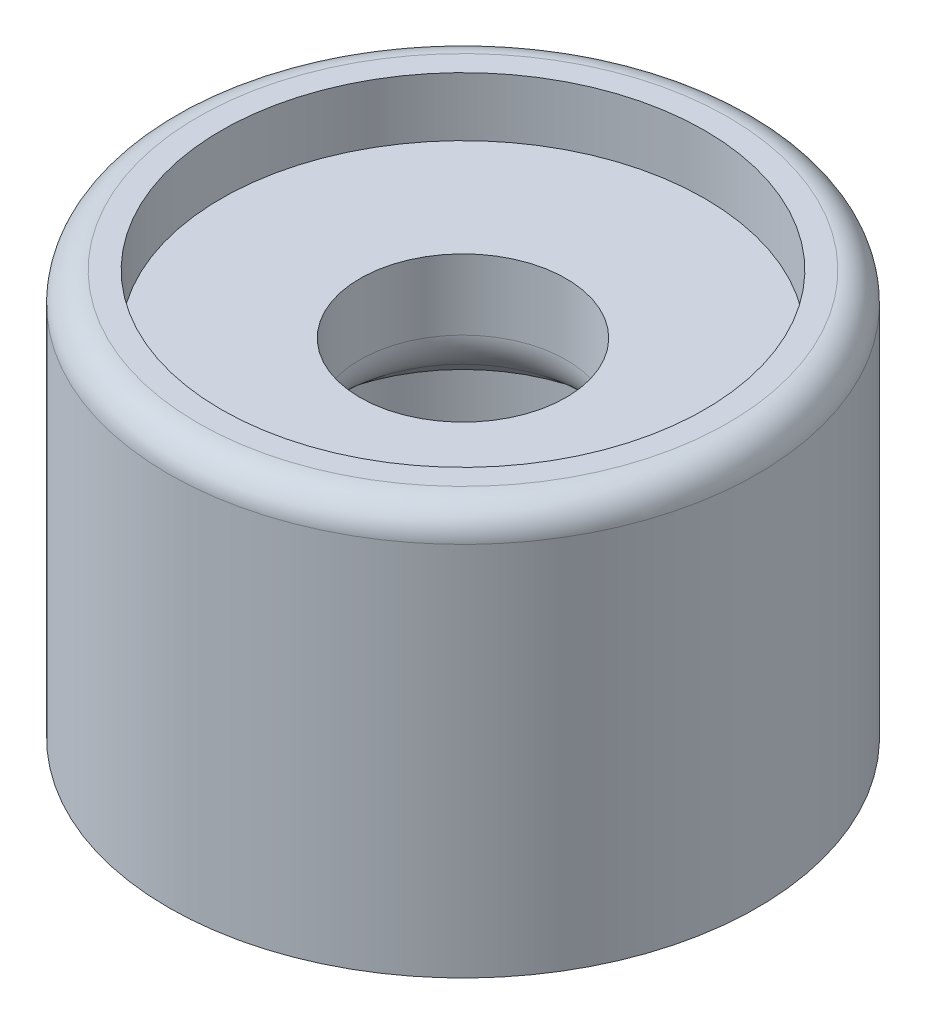
SolidWorks part; units mm, degrees
material "6061-T6 (SS)"
ref_plane "Alzado" through (0, 0, 0) normal (0, 0, 1) x (1, 0, 0)
ref_plane "Planta" through (0, 0, 0) normal (0, 1, 0) x (1, 0, 0)
ref_plane "Vista lateral" through (0, 0, 0) normal (1, 0, 0) x (0, 0, -1)
sketch "Croquis1" plane through (0, 0, 0) normal (0, 1, 0) x (1, 0, 0)
  circle A0 centre (0, 0) radius 3.175
  circle A1 centre (0, 0) radius 6
  dimension "D1" = 12
  dimension "D2" = 6.35
extrude "Saliente-Extruir1" add sketch "Croquis1" along normal blind 4.25
sketch "Croquis2" plane through (0, 0, 0) normal (0, 0, 1) x (1, 0, 0)
  line L0 (-6, 4.25) -> (-6, 5.25)
  line L1 (-6, 5.25) -> (-2.1, 5.25)
  line L2 (-2.1, 5.25) -> (-2.1, 5.15)
  line L3 (-2.1, 5.15) -> (-3.175, 4.25)
  line L4 (6, 4.25) -> (-6, 4.25) construction
  line L5 (0, 0) -> (0, 6.8987) construction
  line L6 (-6, 4.25) -> (-3.175, 4.25)
  dimension "D1" = 4.2
  dimension "D2" = 0.1
  dimension "D3" = 3.9
  dimension "D4" = 1
revolve "Revolución1" add sketch "Croquis2" angle 360 about L5
sketch "Croquis3" plane through (0, 5.25, 0) normal (0, 1, 0) x (1, 0, 0)
  circle A0 centre (0, 0) radius 2.1
  circle A1 centre (0, 0) radius 6
  circle A2 centre (0, 0) radius 6 construction
  circle A3 centre (0, 0) radius 2.1 construction
extrude "Saliente-Extruir2" add sketch "Croquis3" along normal blind 3
fillet "Redondeo1" radius 0.6 1 edges at (0, 8.25, 6)
sketch "Croquis4" plane through (0, 8.25, 0) normal (0, 1, 0) x (1, 0, 0)
  circle A0 centre (0, 0) radius 4.925
  dimension "D1" = 9.85
extrude "Cortar-Extruir1" cut sketch "Croquis4" against normal blind 1.2
sketch "Croquis5" plane through (0, 7.05, 0) normal (0, 1, 0) x (1, 0, 0)
  line L1 (-1.625, 0.0031) -> (1.625, 0.0031)
  line L2 (-1.625, 0.0031) -> (-1.625, 5.0031)
  line L3 (-1.625, 5.0031) -> (1.625, 5.0031)
  line L4 (1.625, 0.0031) -> (1.625, 5.0031)
  point P4 (0, 5.0031)
  dimension "D1" = 3.25
  dimension "D2" = 5
chamfer "Chaflán1" distance 1 angle 45 1 edges at (0, 0, 3.175)
fillet "Redondeo2" radius 1 1 edges at (0, 5.15, -2.1)
